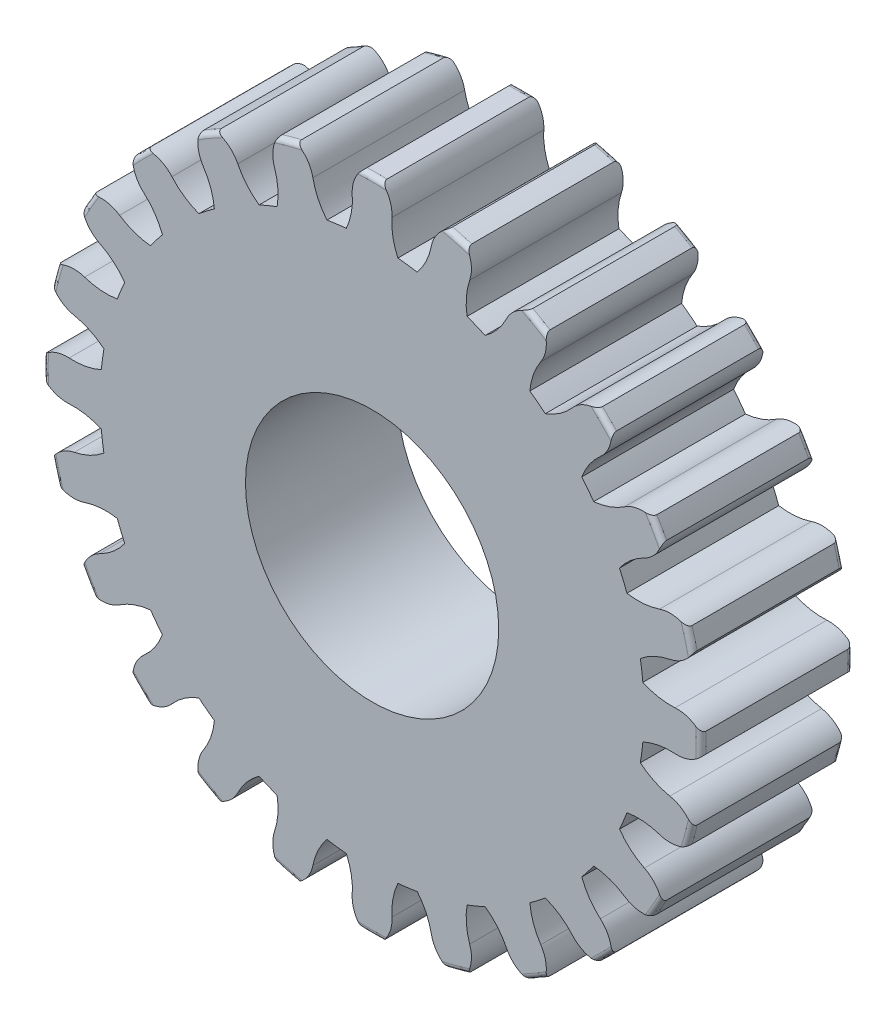
SolidWorks part; units mm, degrees
material "AISI 4130 Steel, annealed at 865C"
ref_plane "Front Plane" through (0, 0, 0) normal (0, 0, 1) x (1, 0, 0)
ref_plane "Top Plane" through (0, 0, 0) normal (0, 1, 0) x (1, 0, 0)
ref_plane "Right Plane" through (0, 0, 0) normal (1, 0, 0) x (0, 0, -1)
sketch "Sketch1" plane through (0, 0, 0) normal (0, 0, 1) x (1, 0, 0)
  circle A0 centre (0, 0) radius 24
  dimension "Pitch circcle" = 48
sketch "Sketch2" plane through (0, 0, 0) normal (0, 0, 1) x (1, 0, 0)
  circle A0 centre (0, 0) radius 21.5
  circle A1 centre (0, 0) radius 26
  circle A2 centre (0, 0) radius 24 construction
  circle A3 centre (0, 0) radius 10.01
  dimension "D1" = 20.02
  dimension "dedendum" = 2.5
  dimension "outercircle" = 2
extrude "Boss-Extrude1" add sketch "Sketch2" along normal mid plane 12 contours A0 A3 region at (-20.8919, 0, 0)
sketch "Sketch3" plane through (0, 0, 0) normal (0, 0, 1) x (1, 0, 0)
  line L0 (0, 0) -> (0, 30.1868) construction
  line L1 (1.5697, 20.5331) -> (1.5697, 28.4748) construction
  line L2 (-1.5697, 23.9486) -> (-6.0944, 92.9824) construction
  line L3 (0, -6.6409) -> (0, 6.6409) construction
  arc A0 (1.5697, 23.9486) -> (-1.5697, 23.9486) centre (0, 0) ccw
  circle A1 centre (0, 0) radius 24 construction
  circle A2 centre (0, 0) radius 21.5 construction
  circle A3 centre (0, 0) radius 26 construction
  arc A4 (-0.7853, 25.9881) -> (0.7853, 25.9881) centre (0, 0) cw
  arc A5 (-2.039, 21.4031) -> (2.039, 21.4031) centre (0, 0) cw
  circle A6 centre (0, 0) radius 21.5 construction
  arc A7 (-2.039, 21.4031) -> (-1.5697, 23.9486) centre (-6.8358, 23.6035) ccw
  arc A8 (-1.5697, 23.9486) -> (-0.7853, 25.9881) centre (1.0308, 24.1191) cw
  arc A9 (2.039, 21.4031) -> (1.5697, 23.9486) centre (6.8358, 23.6035) cw
  arc A10 (1.5697, 23.9486) -> (0.7853, 25.9881) centre (-1.0308, 24.1191) ccw
  point P7 (0, 24)
  dimension "D3" = 0
  dimension "CIrcpitch" = 3.1416
  dimension "D1" = 4.0841
  dimension "D2" = 1.5708
extrude "Boss-Extrude2" add sketch "Sketch3" along normal mid plane 12 contours A8 A7 A5 A9 A10 A4
fillet "Fillet1" radius 0.3927 2 edges at (0, 26, -6) (0, 26, 6)
pattern_circular "CirPattern1" count 24 over 360 about axis through (0, 0, 6) along (0, 0, 1) of "Boss-Extrude2", "Fillet1"
equation "\"Module\"= 2'diameter/nTeeth"
equation "\"nTeeth\"= 24'number of teeth"
equation "\"PressureAngle\"= 10"
equation "\"GearWidth\"= \"Module\" * 6'Thickness of gear"
equation "\"Pitch_Dia\"= \"Module\" * \"nTeeth\"'effectie diameter of gear"
equation "\"Addendum\"= \"Module\""
equation "\"Dedendumm\"= \"Module\" * 1.25"
equation "\"Base_Dia\"= \"Pitch_Dia\" * cos ( \"PressureAngle\" )"
equation "\"Pitch circcle@Sketch1\"=\"Pitch_Dia\""
equation "\"dedendum@Sketch2\"=\"Dedendumm\""
equation "\"outercircle@Sketch2\"=\"Addendum\""
equation "\"D1@Boss-Extrude1\"=\"GearWidth\""
equation "\"CircPitch\"= ( 3.1415926 * \"Pitch_Dia\" ) / ( \"nTeeth\" * 2 )"
equation "\"CIrcpitch@Sketch3\" = \"CircPitch\""
equation "\"D1@CirPattern1\"=\"nTeeth\""
equation "\"Shaft Dia\"=20"
equation "\"D1@Sketch2\"=\"Shaft Dia\"*\"Shaft Apllicator\"?\""
equation "\"FilletR\"= \"CircPitch\" / ( 2 * 4 )"
equation "\"D1@Boss-Extrude2\"=\"GearWidth\""
equation "\"Has Shaft?\"= 1'0 no /1 yes"
equation "\"Shaft Apllicator\"= \"Has Shaft?\" + 0.001"
equation "\"D1@Sketch3\"=\"CircPitch\"*1.3"
equation "\"D2@Sketch3\"=\"CircPitch\"*0.5"
equation "\"D1@Fillet1\"=\"FilletR\""
